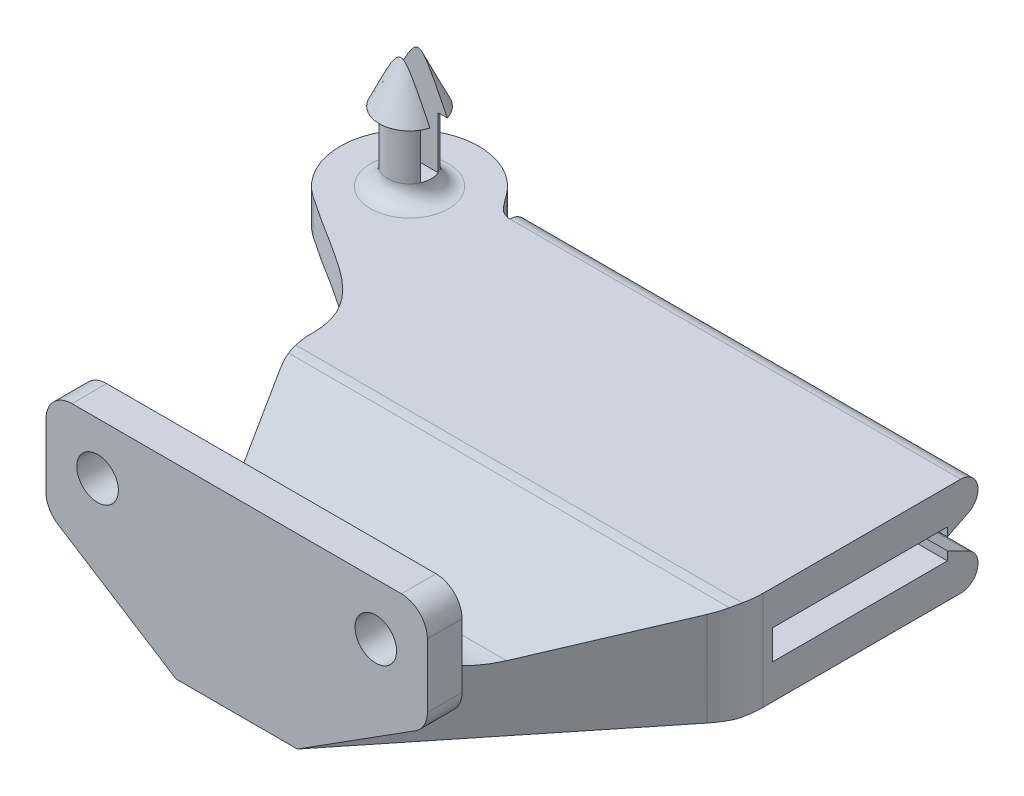
SolidWorks part; units mm, degrees
ref_plane "Front Plane" through (0, 0, 0) normal (0, 0, 1) x (1, 0, 0)
ref_plane "Top Plane" through (0, 0, 0) normal (0, 1, 0) x (1, 0, 0)
ref_plane "Right Plane" through (0, 0, 0) normal (1, 0, 0) x (0, 0, -1)
sketch "Sketch1" plane through (0, 0, 0) normal (0, 1, 0) x (1, 0, 0)
  line L1 (-13, 5) -> (13, 5)
  line L2 (-13, 5) -> (-13, -5)
  line L3 (-13, -5) -> (13, -5)
  line L4 (13, 5) -> (13, -5)
  line L5 (-13, 5) -> (13, -5) construction
  line L6 (-13, -5) -> (13, 5) construction
  point P0 (0, 0)
sketch "Sketch2" plane through (0, 0, 0) normal (0, 1, 0) x (1, 0, 0)
  line L1 (-13, 7) -> (13, 7)
  line L2 (-13, 7) -> (-13, -7)
  line L3 (-13, -7) -> (13, -7)
  line L4 (13, 7) -> (13, -7)
  line L5 (-13, 7) -> (13, -7) construction
  line L6 (-13, -7) -> (13, 7) construction
  point P0 (0, 0)
extrude "Boss-Extrude1" add sketch "Sketch2" along normal blind 2
sketch "Sketch3" plane through (0, 0, 0) normal (0, -1, 0) x (1, 0, 0)
  line L4 (13, -7) -> (13, 7)
  line L5 (13, 7) -> (-13, 7)
  line L6 (-13, 7) -> (-13, -7)
  line L7 (-13, -7) -> (13, -7)
  line L8 (13, -7) -> (13, 7)
  line L9 (13, 7) -> (-13, 7)
  line L10 (-13, 7) -> (-13, -7)
  line L11 (-13, -7) -> (13, -7)
  dimension "D1" = 0
extrude "Boss-Extrude2" add sketch "Sketch3" along normal blind 2 from offset 1.7 separate body
sketch "Sketch4" plane through (0, 0, 0) normal (0, -1, 0) x (1, 0, 0)
  line L1 (-13, 7) -> (13, 7)
  line L2 (-13, 7) -> (-13, 3.1)
  line L3 (-13, 3.1) -> (13, 3.1)
  line L4 (13, 7) -> (13, 3.1)
extrude "Boss-Extrude3" add sketch "Sketch4" along normal blind 2
sketch "Sketch5" plane through (-13, 0, 0) normal (-1, 0, 0) x (0, 0, 1)
  line L0 (-5, 0) -> (-5, -0.5)
  line L3 (5, 0) -> (-5, 0) construction
  line L5 (-5, 0) -> (5, 0) construction
  line L7 (-5, -1.7) -> (-5, -1.2)
  line L9 (3.1, -1.7) -> (-7, -1.7) construction
  line L10 (-5, -0.5) -> (-10, 2)
  line L11 (-10, 2) -> (-5, 2)
  line L12 (-7, 2) -> (7, 2) construction
  line L13 (-5, 2) -> (-5, 0)
  line L14 (-5, -1.7) -> (-5, -3.7)
  line L15 (7, -3.7) -> (-7, -3.7) construction
  line L16 (-5, -3.7) -> (-10, -3.7)
  line L17 (-10, -3.7) -> (-5, -1.2)
  line L18 (-10, 2) -> (-10, -3.7)
  line L19 (-5, -1.2) -> (-5, -0.5)
  line M11 (-7, 2) -> (-7, 0)
  line M12 (-7, 0) -> (3.1, 0)
  line M14 (3.1, -1.7) -> (-7, -1.7)
  line M15 (-7, -1.7) -> (-7, -3.7)
extrude "Cut-Extrude2" cut sketch "Sketch5" against normal blind 233 contours L17 L19 L10 L18 M12 M11 M15 M14 | L10 M12 M11 | L17 M15 M14 region at (-13, -0.85, -8.1989) region at (-13, 0.1667, -6.6667) region at (-13, -1.8667, -6.6667)
extrude "Boss-Extrude4" add sketch "Sketch5<3>" against normal up to surface (26 mm away) contours L17 L7 M14 | L17 L16 M15 | L10 L0 M12 | L11 L10 M11 region at (-13, -0.1667, -5.3333) region at (-13, -1.5333, -5.3333) region at (-13, 1.5, -8) region at (-13, -3.2, -8) up to face at (13, -0.85, -1.98)
sketch "Sketch5<3>" plane through (-13, 0, 0) normal (-1, 0, 0) x (0, 0, 1) same geometry as "Sketch5"
fillet "Fillet1" radius 1 2 edges at (0, -3.7, -10) (0, 2, -10)
sketch "Sketch10" plane through (0, 0, 7) normal (0, 0, 1) x (1, 0, 0)
  line L4 (-13, -3.7) -> (13, -3.7)
  line L5 (13, -3.7) -> (13, 2)
  line L6 (13, 2) -> (-13, 2)
  line L7 (-13, 2) -> (-13, -3.7)
  line L8 (-13, -3.7) -> (13, -3.7)
  line L9 (13, -3.7) -> (13, 2)
  line L10 (13, 2) -> (-13, 2)
  line L11 (-13, 2) -> (-13, -3.7)
  dimension "D1" = 0
sketch3d "3DSketch1" plane through (0, 0, 0) normal (0, 0, 1) x (1, 0, 0)
sketch "Sketch8" plane through (0, 0, 23) normal (0, 0, 1) x (1, 0, 0)
  line L0 (0, -3.7) -> (0, 2) construction
  line L3 (-13, -0.85) -> (13, -0.85) construction
  line L7 (-3.5, 0.15) -> (3.5, 0.15)
  line L8 (-3.5, 0.15) -> (-3.5, -1.85)
  line L9 (-3.5, -1.85) -> (3.5, -1.85)
  line L10 (3.5, 0.15) -> (3.5, -1.85)
  line L11 (-3.5, 0.15) -> (3.5, -1.85) construction
  line L12 (-3.5, -1.85) -> (3.5, 0.15) construction
  point P12 (0, -0.85)
loft "Loft2" add profiles "Sketch10", "Sketch8" connector at (-13, 2, 7) connector at (-3.5, 0.15, 23)
sketch "Sketch9" plane through (0, 0, 23) normal (0, 0, 1) x (1, 0, 0)
  line L0 (0, 8.9074) -> (0, 5.9074) construction
  line L1 (-8.025, 5.9074) -> (8.025, 5.9074) construction
  line L2 (-9.5, 8.9074) -> (9.5, 8.9074)
  line L3 (-11, 7.4074) -> (-11, 3.7322)
  line L4 (-10.3035, 2.4655) -> (-3.5, -1.85)
  line L6 (11, 7.4074) -> (11, 3.7322)
  line L7 (10.3035, 2.4655) -> (3.5, -1.85)
  line L11 (-3.5, -1.85) -> (3.5, -1.85)
  circle A0 centre (-8.025, 5.9074) radius 1.2
  circle A1 centre (8.025, 5.9074) radius 1.2
  arc A2 (11, 3.7322) -> (10.3035, 2.4655) centre (9.5, 3.7322) cw
  arc A3 (9.5, 8.9074) -> (11, 7.4074) centre (9.5, 7.4074) cw
  arc A4 (-9.5, 8.9074) -> (-11, 7.4074) centre (-9.5, 7.4074) ccw
  arc A5 (-11, 3.7322) -> (-10.3035, 2.4655) centre (-9.5, 3.7322) ccw
  point P5 (0, 5.9074)
  point P12 (0, 8.9074)
  dimension "D1" = 1.5
extrude "Boss-Extrude5" add sketch "Sketch9" against normal blind 2 contours L3 A5 L4 L7 A2 L6 A3 L2 A4 A0 A1 region at (0, 4.1004, 23)
sketch "Sketch12" plane through (0, 0, 3.1) normal (0, 0, -1) x (-1, 0, 0)
  line L4 (-13, -1.7) -> (13, -1.7)
  line L5 (13, -1.7) -> (13, 0)
  line L6 (13, 0) -> (-13, 0)
  line L7 (-13, 0) -> (-13, -1.7)
  line L8 (-13, -1.7) -> (13, -1.7)
  line L9 (13, -1.7) -> (13, 0)
  line L10 (13, 0) -> (-13, 0)
  line L11 (-13, 0) -> (-13, -1.7)
  dimension "D1" = 0
extrude "Cut-Extrude5" cut sketch "Sketch12" against normal blind 2
fillet "Fillet2" radius 5 1 edges at (0, 0.3813, 21)
fillet "Fillet5" radius 5 2 edges at (0, -3.7, 7) (0, 2, 7)
fillet "Fillet6" radius 5 2 edges at (13, -0.85, 7) (-13, -0.85, 7)
sketch "Sketch13" plane through (0, 2, 0) normal (0, 1, 0) x (1, 0, 0)
  circle A0 centre (-17.5312, 4.5024) radius 1.375 construction
  circle A1 centre (-17.5312, 4.5024) radius 1.375 construction
  circle A2 centre (-17.5312, 4.5024) radius 1.25
sketch "Sketch14" plane through (0, 2, 0) normal (0, 1, 0) x (1, 0, 0)
  line L0 (13, 5.7639) -> (-13, 5.7639) construction
  line L1 (13, 5.7639) -> (-13, 5.7639) construction
  line L2 (-13, 5.7639) -> (-13, -5.6275) construction
  line L3 (-13, 5.7639) -> (-13, -5.6275)
  arc A0 (-14.2967, 6.8556) -> (-19.8068, 1.2127) centre (-17.5312, 4.5024) ccw
  arc A1 (-13, -5.6275) -> (-12.881, -6.7119) centre (-8, -5.6275) ccw construction
  arc A2 (-13, -5.6275) -> (-12.881, -6.7119) centre (-8, -5.6275) ccw construction
  spline S0 degree 3 poles (-13, -5.6275) (-13, -2.4109) (-15.9147, -1.4796) (-19.8068, 1.2127) knots 0 0 0 0 1 1 1 1
  spline S1 degree 3 poles (-13, 5.7639) (-13.565, 5.7639) (-13.8337, 6.2192) (-14.2967, 6.8556) knots 0 0 0 0 1 1 1 1
extrude "Boss-Extrude6" add sketch "Sketch14" against normal up to surface (2 mm away) up to face at (0, 0, 0.05)
extrude "Boss-Extrude7" add sketch "Sketch13" along normal blind 4 contours A2
fillet "Fillet7" radius 1 1 edges at (-17.5312, 2, -3.2524)
sketch "Sketch15" plane through (0, 6, 0) normal (0, 1, 0) x (1, 0, 0)
  circle A0 centre (-17.5312, 4.5024) radius 1.75
extrude "Boss-Extrude8" add sketch "Sketch15" along normal blind 10 draft 25
sketch "Sketch16" plane through (0, 2, 0) normal (0, 1, 0) x (1, 0, 0)
  line L1 (-20.0312, 5.0024) -> (-15.0312, 5.0024)
  line L2 (-20.0312, 5.0024) -> (-20.0312, 4.0024)
  line L3 (-20.0312, 4.0024) -> (-15.0312, 4.0024)
  line L4 (-15.0312, 5.0024) -> (-15.0312, 4.0024)
  line L5 (-20.0312, 5.0024) -> (-15.0312, 4.0024) construction
  line L6 (-20.0312, 4.0024) -> (-15.0312, 5.0024) construction
  point P0 (-17.5312, 4.5024)
extrude "Cut-Extrude6" cut sketch "Sketch16" along normal blind 10 from offset 1
